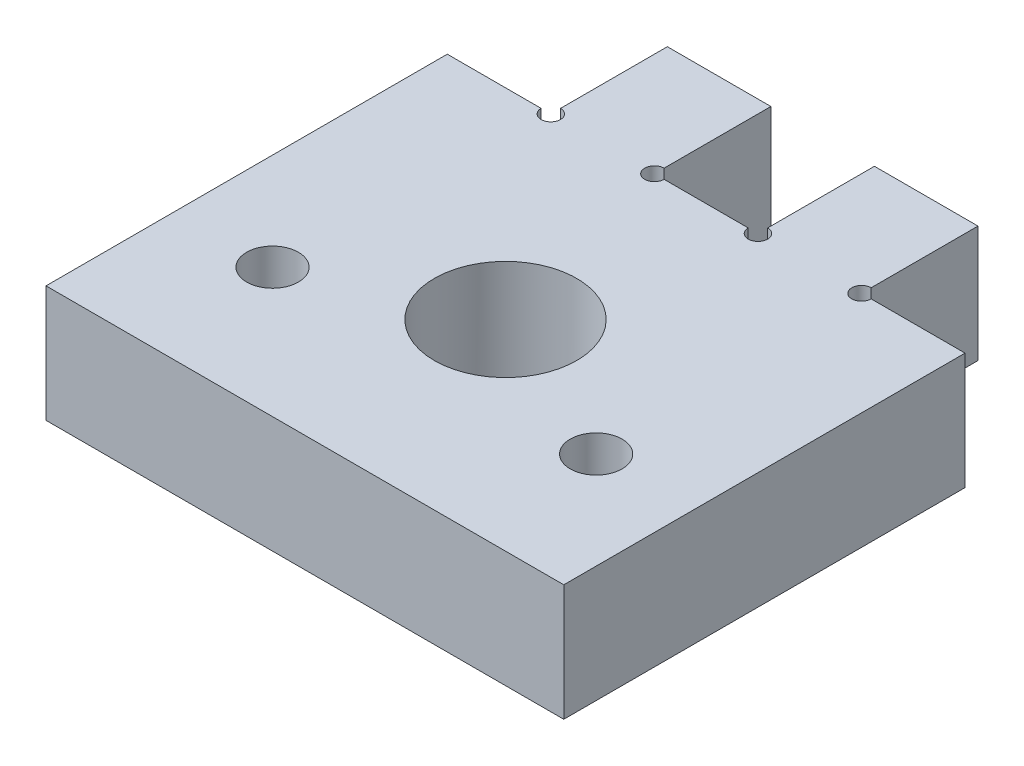
SolidWorks part; units mm, degrees
ref_plane "Front Plane" through (0, 0, 0) normal (0, 0, 1) x (1, 0, 0)
ref_plane "Top Plane" through (0, 0, 0) normal (0, 1, 0) x (1, 0, 0)
ref_plane "Right Plane" through (0, 0, 0) normal (1, 0, 0) x (0, 0, -1)
sketch "Sketch1" plane through (0, 0, 0) normal (0, 1, 0) x (1, 0, 0)
  line L0 (-1000, 0) -> (49000, 0) construction
  line L5 (0, -1000) -> (0, 49000) construction
  line L6 (-40, 31) -> (-24, 31)
  line L7 (-40, -31) -> (40, -31)
  line L8 (-40, -31) -> (-40, 31)
  line L9 (-24, 49) -> (-8, 49)
  line L10 (40, -31) -> (40, 31)
  line L11 (-24, 49) -> (-24, 31)
  line L12 (-8, 49) -> (-8, 31)
  line L13 (8, 49) -> (8, 31)
  line L14 (24, 49) -> (24, 31)
  line L16 (24, 31) -> (40, 31)
  line L17 (8, 49) -> (24, 49)
  line L18 (-8, 31) -> (8, 31)
  circle A10 centre (0, 0) radius 4
  circle A15 centre (25, -11) radius 4
  circle A16 centre (-25, -11) radius 4
  point P6 (0, 31)
  point P7 (0, 0)
  point P9 (0, 0)
  point P10 (-40, 0)
  point P13 (0, 0)
  dimension "D3" = 8
  dimension "D4" = 20
  dimension "D12" = 8
  dimension "D2" = 80
  dimension "D7" = 18
  dimension "D9" = 4
  dimension "D8" = 16
  dimension "D10" = 16
  dimension "D11" = 80
  dimension "D13" = 25
extrude "Boss-Extrude1" add sketch "Sketch1" along normal blind 18
sketch "Sketch2" plane through (0, 18, 0) normal (0, 1, 0) x (1, 0, 0)
  circle A0 centre (0, 0) radius 11
  dimension "D1" = 22
extrude "Cut-Extrude1" cut sketch "Sketch2" against normal up to next
sketch "Sketch3" plane through (0, 18, 0) normal (0, 1, 0) x (1, 0, 0)
  circle A0 centre (-24, 31) radius 1.5
  circle A1 centre (-8, 31) radius 1.5
  circle A2 centre (8, 31) radius 1.5
  circle A3 centre (24, 31) radius 1.5
  dimension "D1" = 3
  dimension "D3" = 16
  dimension "D2" = 4
extrude "Cut-Extrude2" cut sketch "Sketch3" against normal through all
